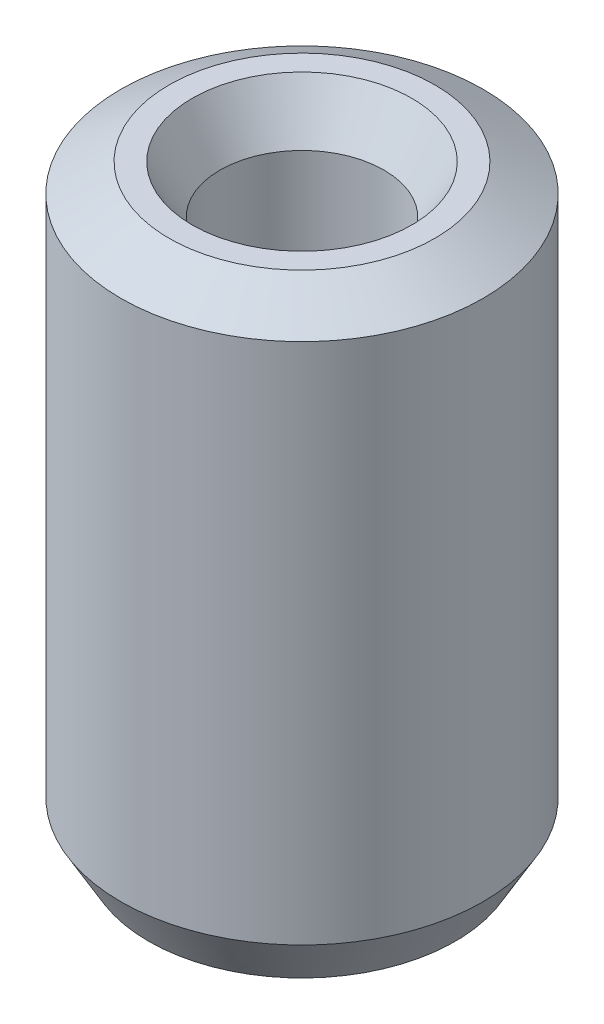
SolidWorks part; units mm, degrees
ref_plane "Front Plane" through (0, 0, 0) normal (0, 0, 1) x (1, 0, 0)
ref_plane "Top Plane" through (0, 0, 0) normal (0, 1, 0) x (1, 0, 0)
ref_plane "Right Plane" through (0, 0, 0) normal (1, 0, 0) x (0, 0, -1)
sketch "Sketch1" plane through (0, 0, 0) normal (0, 1, 0) x (1, 0, 0)
  circle A0 centre (0, 0) radius 17.5
  dimension "SLEEVE_OD" = 35
extrude "Boss-Extrude1" add sketch "Sketch1" along normal blind 57.8313
sketch "Sketch2" plane through (0, 0, 0) normal (0, 1, 0) x (1, 0, 0)
  circle A0 centre (0, 0) radius 7.9175
  dimension "BORE_D" = 15.835
extrude "Cut-Extrude1" cut sketch "Sketch2" along normal through all
chamfer "Chamfer1" distance 2.6902 angle 60 4 edges at (0, 57.8313, 7.9175) (0, 0, 7.9175) (0, 0, 17.5) (0, 57.8313, 17.5) first distance on face at (0, 57.8313, 7.9175) first distance on face at (0, 0, 7.9175) first distance on face at (0, 57.8313, 17.5)
